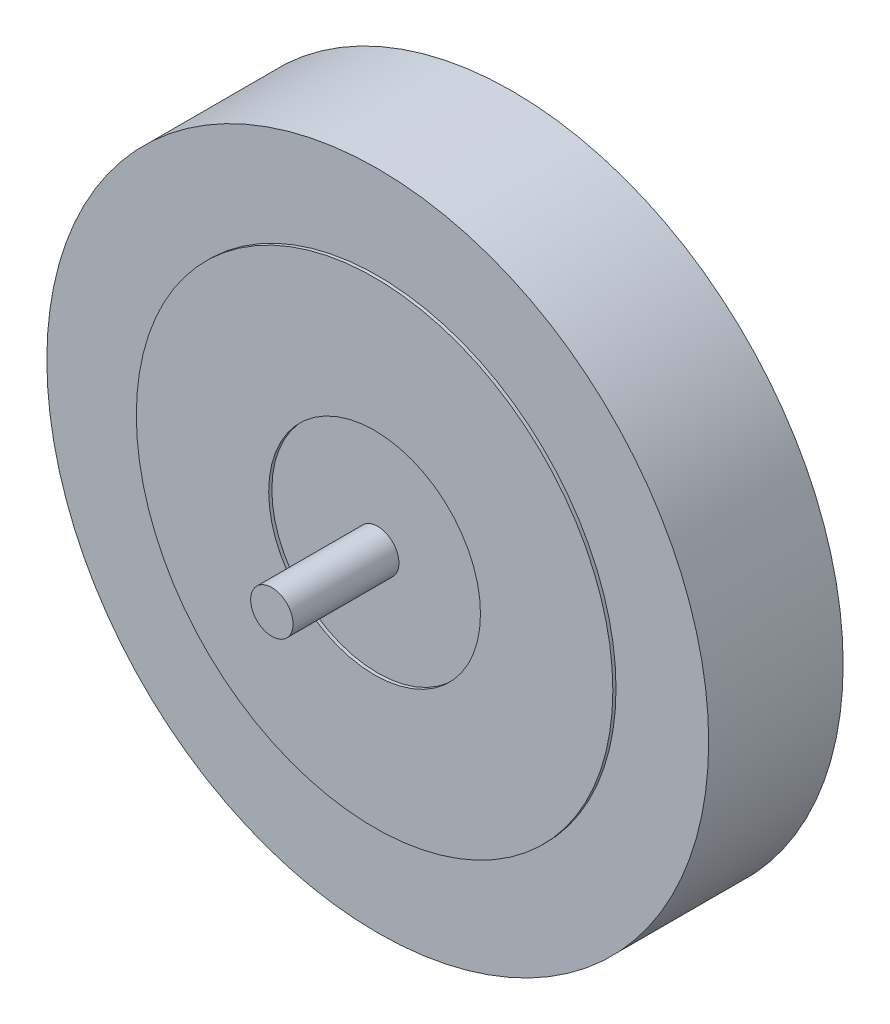
SolidWorks part; units mm, degrees
material "SBR"
ref_plane "Front Plane" through (0, 0, 0) normal (0, 0, 1) x (1, 0, 0)
ref_plane "Top Plane" through (0, 0, 0) normal (0, 1, 0) x (1, 0, 0)
ref_plane "Right Plane" through (0, 0, 0) normal (1, 0, 0) x (0, 0, -1)
sketch "Sketch1" plane through (0, 0, 0) normal (0, 0, 1) x (1, 0, 0)
  circle A0 centre (0, 0) radius 62.5
  circle A1 centre (0, 0) radius 45
  circle A2 centre (0, 0) radius 20
  circle A3 centre (0, 0) radius 4
  dimension "D1" = 125
  dimension "D2" = 90
  dimension "D3" = 40
  dimension "D4" = 8
extrude "Boss-Extrude1" add sketch "Sketch1" along normal blind 25.4 contours A0 A1 | A2 A3 region at (-60.7322, 0, 0) region at (-19.4343, 0, 0)
sketch "Sketch2" plane through (0, 0, 25.4) normal (0, 0, 1) x (1, 0, 0)
  circle A0 centre (0, 0) radius 45
  circle A1 centre (0, 0) radius 20
  dimension "D1" = 90
  dimension "D2" = 40
extrude "Boss-Extrude3" add sketch "Sketch2" against normal blind 26 and the other way blind 0.6
sketch "Sketch3" plane through (0, 0, 25.4) normal (0, 0, 1) x (1, 0, 0)
  circle A0 centre (0, 0) radius 4
  dimension "D1" = 8
extrude "Boss-Extrude4" add sketch "Sketch3" along normal blind 20 separate body
